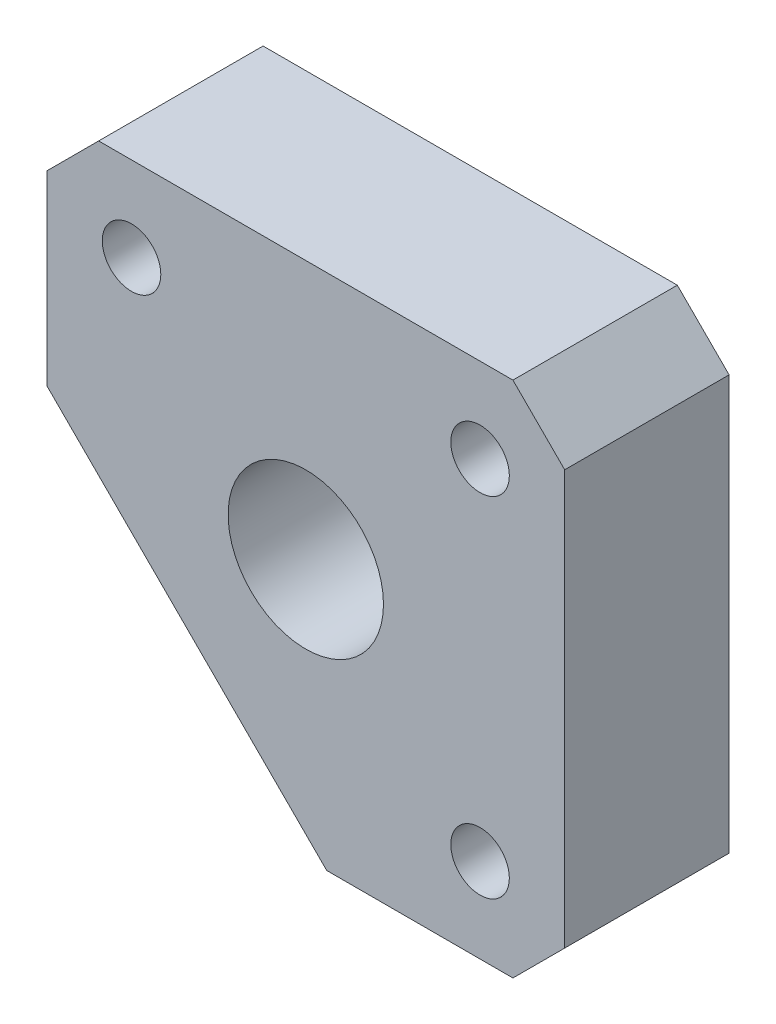
SolidWorks part; units mm, degrees
material "6061-T6 (SS)"
ref_plane "Front" through (0, 0, 0) normal (0, 0, 1) x (1, 0, 0)
ref_plane "Top" through (0, 0, 0) normal (0, 1, 0) x (1, 0, 0)
ref_plane "Right" through (0, 0, 0) normal (1, 0, 0) x (0, 0, -1)
ref_axis "side-side" through (80.9, 0, 0) along (-1, 0, 0)
ref_axis "up-down" through (0, 50, 0) along (0, -1, 0)
ref_axis "front-back" through (0, 0, -80.9) along (0, 0, 1)
sketch "Sketch1" plane through (0, 0, 0) normal (0, 0, 1) x (1, 0, 0)
  line L0 (-10, 0.8076) -> (0.8076, -10)
  line L1 (-10, 10) -> (10, 10)
  line L2 (-10, 10) -> (-10, 0.8076)
  line L3 (0.8076, -10) -> (10, -10)
  line L4 (10, 10) -> (10, -10)
  line L5 (0, 0) -> (10, 0) construction
  line L6 (0, 0) -> (0, 10) construction
  circle A0 centre (0, 0) radius 9.525 construction
  circle A1 centre (0, 0) radius 3
  dimension "D1" = 19.05
  dimension "D2" = 6
  dimension "D3" = 6.5
  dimension "D4" = 20
  dimension "D5" = 45
extrude "Boss-Extrude1" add sketch "Sketch1" along normal blind 6.35
hole_wizard "#4-40 Tapped Hole1" positions "Sketch2" profile "Sketch4" tap size "#4-40" standard "ANSI Inch" end condition through all
sketch "Sketch2" plane through (0, 0, 6.35) normal (0, 0, 1) x (1, 0, 0)
  line L1 (-6.731, 6.731) -> (6.731, 6.731) construction
  line L2 (-6.731, 6.731) -> (-6.731, -6.731) construction
  line L3 (-6.731, -6.731) -> (6.731, -6.731) construction
  line L4 (6.731, 6.731) -> (6.731, -6.731) construction
  line L5 (-6.731, 6.731) -> (6.731, -6.731) construction
  line L6 (10, 10) -> (-10, 10) construction
  point P0 (-6.731, 6.731)
  point P3 (6.731, -6.731)
  point P56 (-6.731, -6.731)
  point P57 (6.731, 6.731)
  dimension "D1" = 13.462
  dimension "D2" = 3.269
sketch "Sketch4" plane through (-6.731, 6.731, 6.35) normal (1, 0, 0) x (0, -1, 0)
  line L0 (0, 0) -> (0, 6.35)
  line L1 (0, 6.35) -> (1.1303, 6.35)
  line L2 (1.1303, 6.35) -> (1.1303, 0)
  line L5 (1.1303, 0) -> (0, 0)
  line L11 (0, -6.35) -> (0, 107.95) construction
  dimension "Thru Tap Drill Dia." = 2.2606
  dimension "Thru Tap Drill Depth" = 6.35
cosmetic thread "Hole Thread1" parameters "D2"=2.8448
cosmetic thread "Hole Thread3" parameters "D2"=2.8448
cosmetic thread "Hole Thread4" parameters "D2"=2.8448
chamfer "Chamfer1" distance 2 angle 45 3 edges at (10, -10, 3.175) (10, 10, 3.175) (-10, 10, 3.175)
